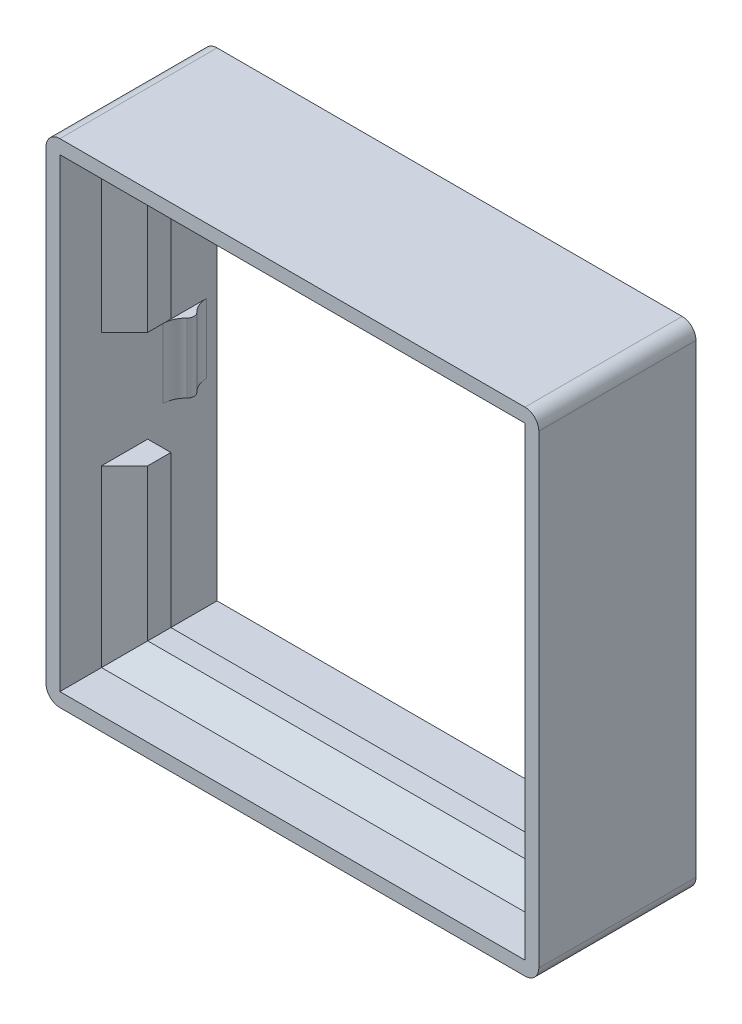
SolidWorks part; units mm, degrees
ref_plane "Front Plane" through (0, 0, 0) normal (1, 0, 0) x (0, 1, 0)
ref_plane "Top Plane" through (0, 0, 0) normal (0, 0, 1) x (0, 1, 0)
ref_plane "Right Plane" through (0, 0, 0) normal (0, 1, 0) x (-1, 0, 0)
ref_axis "center_axis-Z" through (0, 0, 210) along (0, 0, -1)
sketch "Sketch1" plane through (0, 0, 0) normal (0, 0, 1) x (0, 1, 0)
  line L1 (50.3, -50.3) -> (-50.3, -50.3)
  line L2 (50.3, -50.3) -> (50.3, 50.3)
  line L3 (50.3, 50.3) -> (-50.3, 50.3)
  line L4 (-50.3, -50.3) -> (-50.3, 50.3)
  line L5 (50.3, -50.3) -> (-50.3, 50.3) construction
  line L6 (50.3, 50.3) -> (-50.3, -50.3) construction
  line L7 (53.3, -53.3) -> (-53.3, -53.3)
  line L8 (53.3, -53.3) -> (53.3, 53.3)
  line L9 (53.3, 53.3) -> (-53.3, 53.3)
  line L10 (-53.3, -53.3) -> (-53.3, 53.3)
  line L11 (53.3, -53.3) -> (-53.3, 53.3) construction
  line L12 (53.3, 53.3) -> (-53.3, -53.3) construction
  point P0 (0, 0)
  point P6 (0, 0)
  dimension "D1" = 100.6
  dimension "D2" = 100.6
  dimension "D4" = 3
  dimension "D3" = 3
extrude "Boss-Extrude1" add sketch "Sketch1" along normal blind 200
sketch "Sketch2" plane through (0, 0, 0) normal (1, 0, 0) x (0, 1, 0)
  line L0 (0, -58.63) -> (0, 58.63) construction
  line L1 (37.5, 192.5) -> (-37.5, 192.5)
  line L2 (37.5, 192.5) -> (37.5, 182.5)
  line L3 (37.5, 182.5) -> (-37.5, 182.5)
  line L4 (-37.5, 192.5) -> (-37.5, 182.5)
  line L5 (37.5, 192.5) -> (-37.5, 182.5) construction
  line L6 (37.5, 182.5) -> (-37.5, 192.5) construction
  line L7 (-53.3, 200) -> (53.3, 200) construction
  line L8 (0, 200) -> (0, 0) construction
  line L9 (37.5, 177.5) -> (-37.5, 177.5)
  line L10 (-37.5, 177.5) -> (-37.5, 167.5)
  line L11 (37.5, 167.5) -> (-37.5, 167.5)
  line L12 (37.5, 177.5) -> (37.5, 167.5)
  line L13 (37.5, 162.5) -> (-37.5, 162.5)
  line L14 (-37.5, 162.5) -> (-37.5, 152.5)
  line L15 (37.5, 152.5) -> (-37.5, 152.5)
  line L16 (37.5, 162.5) -> (37.5, 152.5)
  point P0 (0, 187.5)
  dimension "D1" = 10
  dimension "D2" = 75
  dimension "D3" = 12.5
  dimension "D4" = 3
extrude "Cut-Extrude1" cut sketch "Sketch2" against normal through all both and the other way through all
pattern_circular "CirPattern1" count 2 over 90 about axis through (0, 0, 210) along (0, 0, -1) of "Cut-Extrude1"
fillet "Fillet1" radius 3 4 edges at (-53.3, 53.3, 100) (-53.3, -53.3, 100) (53.3, -53.3, 100) (53.3, 53.3, 100)
ref_plane "interface_plane" through (0, 0, 15) normal (0, 0, 1) x (0, 1, 0)
sketch "Sketch3" plane through (0, 0, 15) normal (0, 0, 1) x (0, 1, 0)
  line L0 (-50.3, -50.3) -> (50.3, -50.3) construction
  line L1 (50.3, -50.3) -> (50.3, 50.3) construction
  line L2 (50.3, 50.3) -> (-50.3, 50.3) construction
  line L3 (-50.3, 50.3) -> (-50.3, -50.3) construction
  line L4 (-50.3, -50.3) -> (-12.5, -50.3)
  line L5 (50.3, -50.3) -> (50.3, 50.3)
  line L6 (50.3, 50.3) -> (12.5, 50.3)
  line L7 (-50.3, 50.3) -> (-50.3, -50.3)
  line L8 (-45.3, 45.3) -> (-45.3, -45.3)
  line L9 (-45.3, -45.3) -> (-12.5, -45.3)
  line L10 (45.3, -45.3) -> (45.3, 45.3)
  line L11 (45.3, 45.3) -> (12.5, 45.3)
  line L12 (-12.5, 50.3) -> (-12.5, 45.3)
  line L13 (12.5, 50.3) -> (12.5, 45.3)
  line L15 (0, -58.63) -> (0, 58.63) construction
  line L16 (-58.63, 0) -> (58.63, 0) construction
  line L17 (12.5, -50.3) -> (12.5, -45.3)
  line L18 (-12.5, -50.3) -> (-12.5, -45.3)
  line L19 (-12.5, 45.3) -> (-45.3, 45.3)
  line L20 (-12.5, 50.3) -> (-50.3, 50.3)
  line L21 (45.3, 45.3) -> (-45.3, 45.3) construction
  line L22 (12.5, -45.3) -> (45.3, -45.3)
  line L23 (50.3, 50.3) -> (-50.3, 50.3) construction
  line L24 (12.5, -50.3) -> (50.3, -50.3)
  line L25 (-45.3, -45.3) -> (45.3, -45.3) construction
  line L27 (-50.3, -50.3) -> (50.3, -50.3) construction
  dimension "D2" = 25
  dimension "D3" = 12.5
  dimension "D1" = 5
extrude "Boss-Extrude2" add sketch "Sketch3" along normal blind 5
sketch "Sketch4" plane through (0, 0, 0) normal (0, 1, 0) x (-1, 0, 0)
  line L2 (0, 58.63) -> (0, -58.63) construction
  line L3 (58.63, 15) -> (-58.63, 15) construction
  circle A0 centre (49.8, 7) radius 1.5
  point P2 (48.3, 7)
  point P4 (0, 0)
  point P8 (0, 0)
  dimension "D2" = 3
  dimension "D1" = 49.8
  dimension "D3" = 8
extrude "Boss-Extrude3" add sketch "Sketch4" along normal mid plane 15
sketch "Sketch6" plane through (0, 0, 0) normal (0, 1, 0) x (-1, 0, 0)
  line L0 (50.3, 200) -> (50.3, 0) construction
  line L1 (51.6, 13) -> (52, 13)
  line L2 (51.3, 12.7) -> (51.3, 1.3)
  line L3 (51.6, 1) -> (52, 1)
  line L4 (52.3, 12.7) -> (52.3, 1.3)
  line L5 (53.3, 0) -> (53.3, 200) construction
  line L6 (51.6, 13) -> (51.3, 12.7)
  line L7 (52, 13) -> (52.3, 12.7)
  line L8 (52.3, 1.3) -> (52, 1)
  line L9 (51.3, 1.3) -> (51.6, 1)
  arc A0 (50.3, 8.4142) -> (50.3, 5.5858) centre (49.8, 7) ccw construction
  point P0 (51.3, 13)
  point P1 (52.3, 1)
  point P2 (51.3, 1)
  point P3 (52.3, 13)
  dimension "D1" = 1
  dimension "D2" = 1
  dimension "D3" = 12
  dimension "D4" = 6
extrude "Cut-Extrude3" cut sketch "Sketch6" against normal mid plane 20
fillet "Fillet2" radius 5 2 edges at (-50.3, 0, 5.5858) (-50.3, 0, 8.4142)
mirror "Mirror3" about plane through (0, 0, 0) normal (1, 0, 0) of "Fillet2", "Cut-Extrude3", "Boss-Extrude3"
chamfer "Chamfer1" distance 5 angle 45 6 edges at (50.3, 31.4, 20) (0, 50.3, 20) (-50.3, 31.4, 20) (-50.3, -31.4, 20) (0, -50.3, 20) (50.3, -31.4, 20)
sketch "Sketch7" plane through (0, 0, 200) normal (0, 0, 1) x (1, 0, 0)
  line L1 (84.495, -59.5436) -> (-84.495, -59.5436)
  line L2 (84.495, -59.5436) -> (84.495, 59.5436)
  line L3 (84.495, 59.5436) -> (-84.495, 59.5436)
  line L4 (-84.495, -59.5436) -> (-84.495, 59.5436)
  line L5 (84.495, -59.5436) -> (-84.495, 59.5436) construction
  line L6 (84.495, 59.5436) -> (-84.495, -59.5436) construction
  point P0 (0, 0)
extrude "test_piece" cut sketch "Sketch7" against normal blind 166
equation "\"D3@Sketch1\"=\"D4@Sketch1\""
equation "\"D1@Sketch1\"=\"D2@Sketch1\""
equation "\"D3@Sketch3\"=\"D2@Sketch3\"/2"
equation "\"D4@Sketch6\"=\"D3@Sketch6\"/2"
